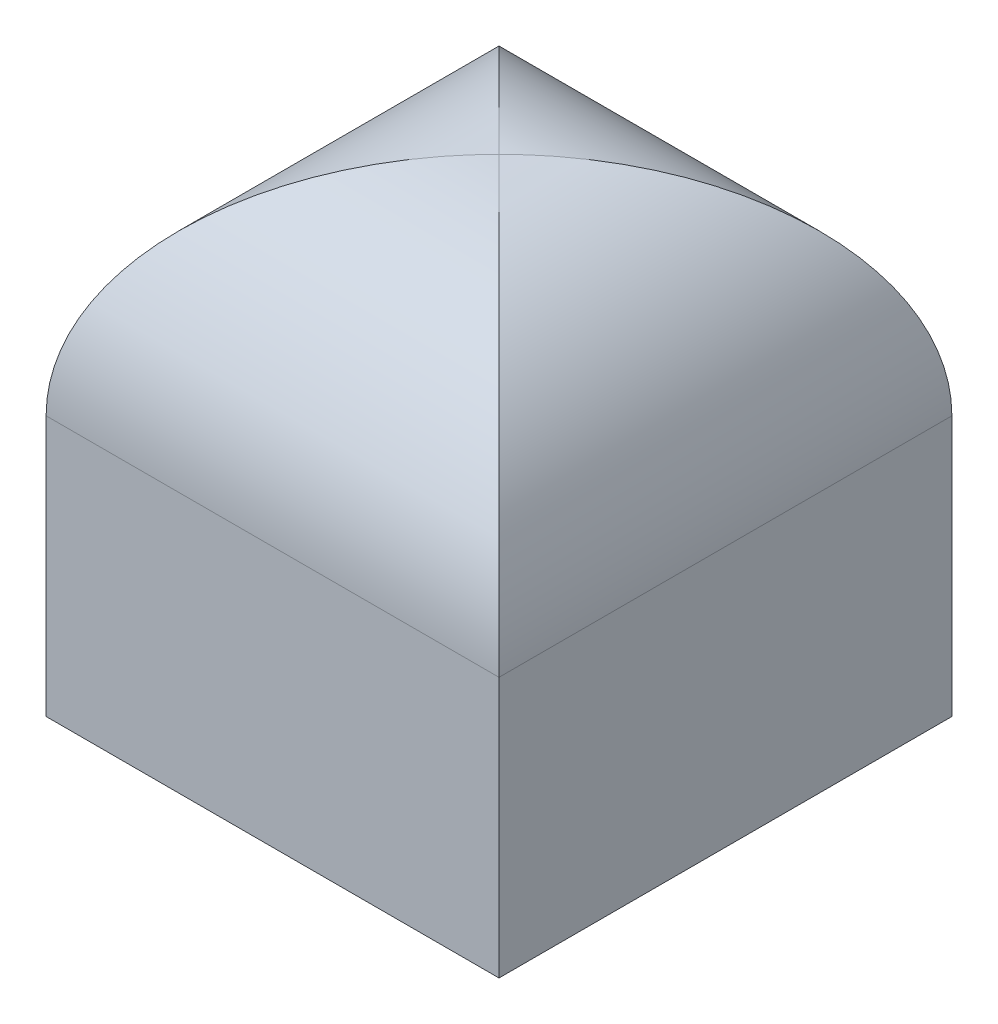
SolidWorks part; units mm, degrees
ref_plane "Front Plane" through (0, 0, 0) normal (0, 0, 1) x (1, 0, 0)
ref_plane "Top Plane" through (0, 0, 0) normal (0, 1, 0) x (1, 0, 0)
ref_plane "Right Plane" through (0, 0, 0) normal (1, 0, 0) x (0, 0, -1)
sketch "Sketch1" plane through (0, 0, 0) normal (0, 1, 0) x (1, 0, 0)
  line L1 (-20, 20) -> (20, 20)
  line L2 (-20, 20) -> (-20, -20)
  line L3 (-20, -20) -> (20, -20)
  line L4 (20, 20) -> (20, -20)
  line L5 (-20, 20) -> (20, -20) construction
  line L6 (-20, -20) -> (20, 20) construction
  point P0 (0, 0)
  dimension "D1" = 40
  dimension "D2" = 40
extrude "Boss-Extrude4" add sketch "Sketch1" along normal blind 43
fillet "Fillet1" radius 20 4 edges at (0, 43, 20) (-20, 43, 0) (0, 43, -20) (20, 43, 0)
